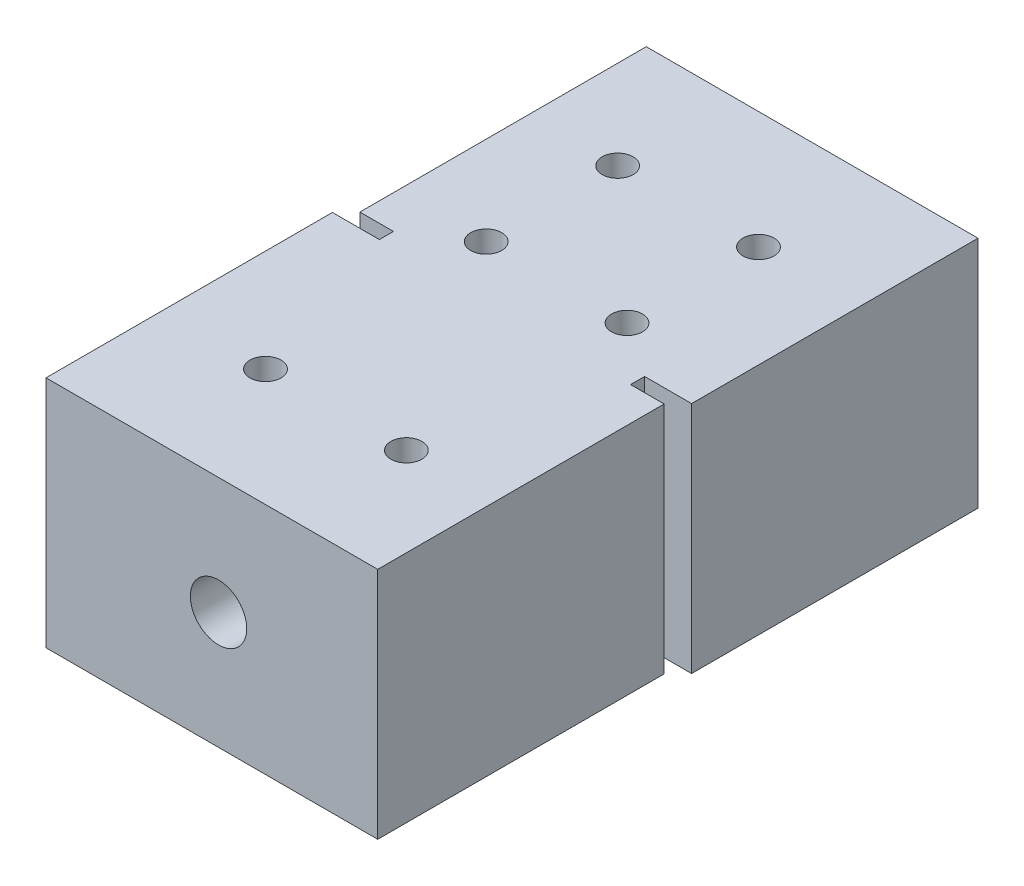
SolidWorks part; units mm, degrees
material "Beech"
ref_plane "Front Plane" through (0, 0, 0) normal (0, 0, 1) x (1, 0, 0)
ref_plane "Top Plane" through (0, 0, 0) normal (0, 1, 0) x (1, 0, 0)
ref_plane "Right Plane" through (0, 0, 0) normal (1, 0, 0) x (0, 0, -1)
sketch "Sketch1" plane through (0, 0, 0) normal (0, 0, 1) x (1, 0, 0)
  line L1 (0, 0) -> (73.5, 0)
  line L2 (0, 0) -> (0, 49.8)
  line L3 (0, 49.8) -> (73.5, 49.8)
  line L4 (73.5, 0) -> (73.5, 49.8)
  dimension "D1" = 73.5
  dimension "D2" = 49.8
extrude "slider body" add sketch "Sketch1" along normal blind 125
sketch "Sketch2" plane through (0, 0, 0) normal (0, 0, -1) x (-1, 0, 0)
  line L0 (-73.5, 49.8) -> (0, 0) construction
  line L1 (-73.5, 0) -> (0, 49.8) construction
  circle A0 centre (-36.75, 24.9) radius 11
  dimension "D1" = 22
extrude "lead nut inset" cut sketch "Sketch2" against normal blind 15
sketch "Sketch3" plane through (0, 0, 15) normal (0, 0, -1) x (-1, 0, 0)
  circle A0 centre (-36.75, 24.9) radius 6
  circle A1 centre (-36.75, 24.9) radius 11 construction
  dimension "D1" = 12
extrude "leadscrew clearance" cut sketch "Sketch3" against normal through all
sketch "Sketch9" plane through (0, 0, 0) normal (0, -1, 0) x (1, 0, 0)
  line L0 (73.5, 125) -> (73.5, 0) construction
  line L1 (73.5, 64) -> (63.5, 64)
  line L2 (73.5, 64) -> (73.5, 61)
  line L3 (73.5, 61) -> (63.5, 61)
  line L4 (63.5, 64) -> (63.5, 61)
  point P6 (73.5, 62.5)
  point P7 (73.5, 62.5)
  dimension "D1" = 10
  dimension "D2" = 3
extrude "decoupling slit" cut sketch "Sketch9" against normal through all
hole_wizard "bolt clearance holes" positions "Sketch4" profile "Sketch6" hole size "M6" standard "ANSI Metric" end condition through all
sketch "Sketch4" plane through (0, 49.8, 0) normal (0, 1, 0) x (1, 0, 0)
  line L1 (51.75, -100) -> (21.75, -100)
  line L2 (51.75, -100) -> (51.75, -25)
  line L3 (51.75, -25) -> (21.75, -25)
  line L4 (21.75, -100) -> (21.75, -25)
  line L10 (21.75, -62.5) -> (0, -62.5)
  line L11 (0, -125) -> (0, 0) construction
  line L13 (36.75, -100) -> (36.75, -125)
  line L14 (73.5, -125) -> (0, -125) construction
  point P1 (51.75, -100)
  point P2 (21.75, -25)
  point P47 (51.75, -25)
  point P48 (21.75, -100)
  point P72 (21.75, -53)
  point P74 (51.75, -53)
  dimension "D1" = 30
  dimension "D2" = 75
  dimension "D3" = 28
sketch "Sketch6" plane through (51.75, 49.8, 100) normal (1, 0, 0) x (0, 0, 1)
  line L0 (0, 0) -> (0, 49.8)
  line L1 (0, 49.8) -> (3.3, 49.8)
  line L2 (3.3, 49.8) -> (3.3, 0)
  line L5 (3.3, 0) -> (0, 0)
  line L11 (0, -6.35) -> (0, 107.95) construction
  dimension "Thru Hole Dia." = 6.6
  dimension "Thru Hole Depth" = 49.8
sketch "Sketch7" plane through (0, 0, 0) normal (0, -1, 0) x (1, 0, 0)
  circle A0 centre (21.75, 100) radius 6
  circle A1 centre (51.75, 100) radius 6
  circle A2 centre (51.75, 25) radius 6
  circle A3 centre (21.75, 25) radius 6
  dimension "D1" = 12
extrude "nut clearance counterbores" [suppressed] cut sketch "Sketch7" against normal blind 10
ref_plane "midplane along length" through (36.75, 0, 0) normal (-1, 0, 0) x (0, 0, 1)
mirror "mirror slit" about plane through (36.75, 0, 0) normal (-1, 0, 0) of "decoupling slit"
sketch "Sketch10" plane through (0, 0, 0) normal (0, -1, 0) x (1, 0, 0)
  line L0 (73.5, 64) -> (63.5, 64) construction
  line L1 (73.5, 125) -> (70.65, 125)
  line L2 (73.5, 125) -> (73.5, 64)
  line L3 (73.5, 64) -> (70.65, 64)
  line L4 (70.65, 125) -> (70.65, 64)
  line L5 (0, 0) -> (73.5, 0) construction
  line L6 (0, 61) -> (2.85, 61)
  line L7 (0, 61) -> (0, 0)
  line L8 (0, 0) -> (2.85, 0)
  line L9 (2.85, 61) -> (2.85, 0)
  dimension "D1" = 2.85
extrude "neoprene inlay" cut sketch "Sketch10" against normal through all
equation "\"board_thickness\"= 18mm"
equation "\"way_width\"= 75mm"
equation "\"way_thickness\"= 50mm"
equation "\"radial_clearance\"= 0.1mm"
equation "\"slider_width\"= \"way_width\"-2* \"radial_clearance\" - 2*0.65"
equation "\"slider_thickness\"= \"way_thickness\" - 2 * \"radial_clearance\""
equation "\"column_width\"= \"way_width\" + 2 * \"board_thickness\""
equation "\"boxway_slot_width\"= 50mm"
equation "\"keeper_rail_width\"= (\"column_width\" - \"boxway_slot_width\")/2"
equation "\"slider_length\"= 125mm"
equation "\"D1@Sketch1\"=\"slider_width\""
equation "\"D2@Sketch1\"=\"slider_thickness\""
equation "\"D1@slider body\" = \"slider_length\""
equation "\"nut_diameter\"= 22mm"
equation "\"nut_length\"= 15mm"
equation "\"D1@Sketch2\"=\"nut_diameter\""
equation "\"D1@lead nut inset\" = \"nut_length\""
equation "\"leadscrew_diameter\"= 10mm"
equation "\"leadscrew_radial_clearance\"= 1mm"
equation "\"D1@Sketch3\"=\"leadscrew_diameter\"+2* \"leadscrew_radial_clearance\""
equation "\"bearing_bolt_pattern_width\"= 30mm"
equation "\"bearing_bolt_pattern_height\"= 75mm"
equation "\"desktop_bolt_pattern_width\"= 30mm"
equation "\"desktop_bolt_pattern_height\"= 30mm"
equation "\"D1@Sketch4\"=\"bearing_bolt_pattern_width\""
equation "\"D2@Sketch4\"=\"bearing_bolt_pattern_height\""
equation "\"bearing_bolt_nut_counterbore_diameter\"= 12mm"
equation "\"bearing_bolt_nut_counterbore_depth\"= 10mm"
equation "\"D1@Sketch7\"=\"bearing_bolt_nut_counterbore_diameter\""
equation "\"D1@nut clearance counterbores\" = \"bearing_bolt_nut_counterbore_depth\""
equation "\"D1@Sketch10\"=3.5-0.65"
